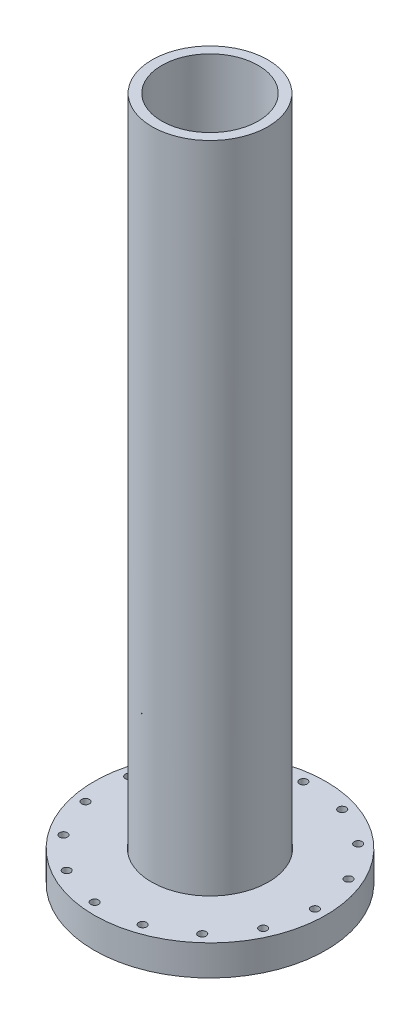
SolidWorks part; units mm, degrees
material "AISI 316 Stainless Steel Sheet (SS)"
ref_plane "Front Plane" through (0, 0, 0) normal (0, 0, 1) x (1, 0, 0)
ref_plane "Top Plane" through (0, 0, 0) normal (0, 1, 0) x (1, 0, 0)
ref_plane "Right Plane" through (0, 0, 0) normal (1, 0, 0) x (0, 0, -1)
sketch "Sketch1" plane through (0, 0, 0) normal (0, 1, 0) x (1, 0, 0)
  circle A0 centre (0, 0) radius 31.75
  circle A1 centre (0, 0) radius 38.1
  dimension "D1" = 63.5
  dimension "D2" = 76.2
extrude "Boss-Extrude1" add sketch "Sketch1" along normal blind 450
sketch "Sketch2" plane through (0, 0, 0) normal (0, 1, 0) x (1, 0, 0)
  circle A0 centre (0, 0) radius 76.2
  circle A3 centre (0, 0) radius 76.2 construction
  circle A4 centre (0, 0) radius 38.4556
  circle A5 centre (0, 0) radius 38.1 construction
  dimension "D1" = 0.3556
extrude "Boss-Extrude2" add sketch "Sketch2" along normal blind 20 separate body
hole_wizard "13/64 (0.20313) Diameter Hole1" positions "Sketch4" profile "Sketch5" hole size "13/64" standard "ANSI Inch" end condition through all
sketch "Sketch4" plane through (0, 0, 0) normal (0, -1, 0) x (-1, 0, 0)
  point P0 (-69, 0)
  dimension "D1" = 69
sketch "Sketch5" plane through (69, 0, 0) normal (1, 0, 0) x (0, 0, -1)
  line L0 (0, 0) -> (0, 450)
  line L1 (0, 450) -> (2.5798, 450)
  line L2 (2.5798, 450) -> (2.5798, 0)
  line L5 (2.5798, 0) -> (0, 0)
  line L11 (0, -6.35) -> (0, 107.95) construction
  dimension "Thru Hole Dia." = 5.1595
  dimension "Thru Hole Depth" = 450
ref_axis "Axis1" through (0, 472.5, 0) along (0, -1, 0)
pattern_circular "CirPattern1" count 15 over 360 about axis through (0, 472.5, 0) along (0, -1, 0) of "13/64 (0.20313) Diameter Hole1"
sketch "Sketch6" plane through (0, 0, 0) normal (0, -1, 0) x (1, 0, 0)
  circle A0 centre (0, 0) radius 55.14 construction
  circle A1 centre (0, 0) radius 55.14
extrude "Cut-Extrude1" cut sketch "Sketch6" against normal blind 2
